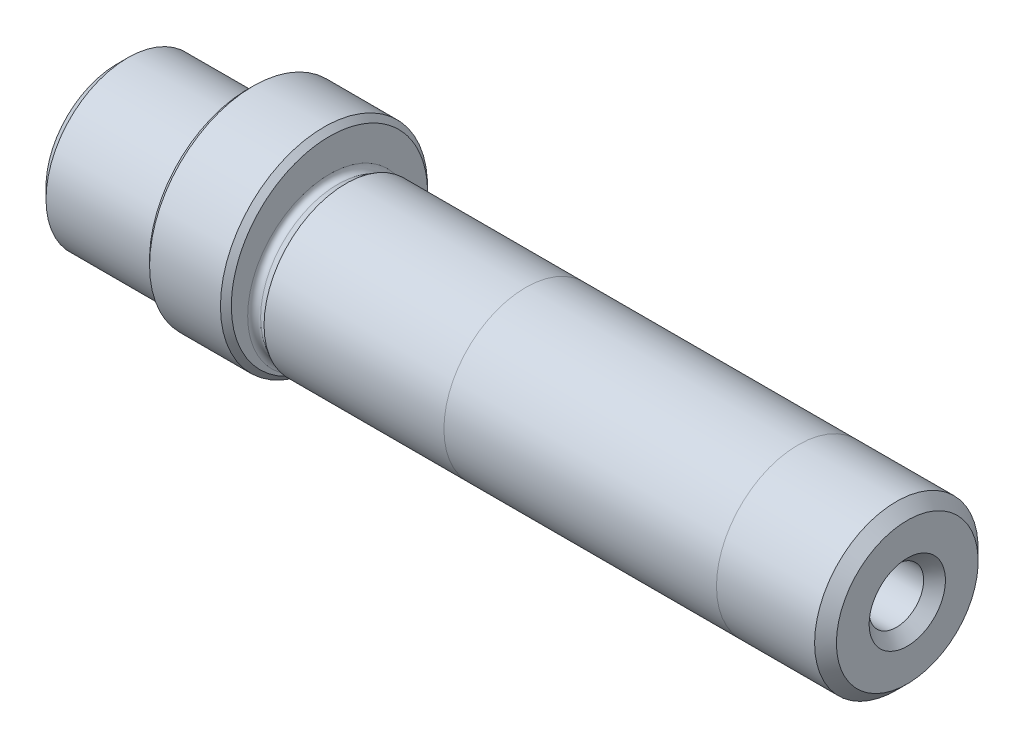
SolidWorks part; units mm, degrees
material "Cast Carbon Steel"
ref_plane "Front Plane" through (0, 0, 0) normal (0, 0, 1) x (1, 0, 0)
ref_plane "Top Plane" through (0, 0, 0) normal (0, 1, 0) x (1, 0, 0)
ref_plane "Right Plane" through (0, 0, 0) normal (1, 0, 0) x (0, 0, -1)
sketch "Sketch2" plane through (0, 0, 0) normal (0, 0, 1) x (1, 0, 0)
  line L0 (0, 0) -> (145, 0)
  line L1 (145, 0) -> (145, 15)
  line L2 (145, 15) -> (39, 15)
  line L3 (39, 15) -> (39, 25)
  line L4 (39, 25) -> (24, 25)
  line L5 (24, 25) -> (24, 15.2)
  line L6 (24, 15.2) -> (0, 15.2)
  line L7 (0, 15.2) -> (0, 0)
  line L8 (20, -25.2984) -> (20, 61.1316) construction
  dimension "D1" = 145
  dimension "D2" = 15
  dimension "D3" = 15
  dimension "D4" = 20
  dimension "D5" = 15.2
  dimension "D6" = 25
  dimension "D7" = 4
revolve "Revolve1" add sketch "Sketch2" angle 360 about L0
sketch "Sketch3" plane through (24, 0, 0) normal (-1, 0, 0) x (0, 0, 1)
  line L0 (0, 0) -> (0, 23.8099) construction
  circle A0 centre (0, 3) radius 19
  dimension "D1" = 38
  dimension "D2" = 3
extrude "Cut-Extrude1" cut sketch "Sketch3" against normal through all both and the other way through all flip side to cut
sketch "Sketch4" plane through (0, 0, 0) normal (0, 0, 1) x (1, 0, 0)
  line L0 (-1.2271, 15) -> (21, 15)
  line L1 (21, 15) -> (22.5, 14.134)
  line L2 (24, 15) -> (24, 19.0868)
  line L3 (24, 19.0868) -> (-1.2271, 19.0868)
  line L4 (-1.2271, 19.0868) -> (-1.2271, 15)
  line L5 (24, 22) -> (24, -16) construction
  line L6 (0, 0) -> (19.6384, 0) construction
  line L7 (147.3282, 15) -> (42, 15)
  line L8 (42, 15) -> (40.5, 14.134)
  line L9 (39, 15) -> (39, 21.5061)
  line L10 (39, 21.5061) -> (147.3282, 21.5061)
  line L11 (147.3282, 21.5061) -> (147.3282, 15)
  line L12 (39, -16) -> (39, 22) construction
  arc A0 (22.5, 14.134) -> (24, 15) centre (23, 15) ccw
  arc A1 (40.5, 14.134) -> (39, 15) centre (40, 15) cw
  dimension "D4" = 1
  dimension "D8" = 1
  dimension "D1" = 15
  dimension "D2" = 30
  dimension "D3" = 3
  dimension "D5" = 30
  dimension "D6" = 3
  dimension "D7" = 15
revolve "Cut-Revolve1" cut sketch "Sketch4" angle 360 about L6
chamfer "Chamfer1" distance 1 angle 45 2 edges at (39, 3, 19) (24, 3, -19)
sketch "Sketch6" plane through (0, 0, 0) normal (-1, 0, 0) x (0, 0, 1)
  circle A0 centre (0, 0) radius 5
  dimension "D1" = 10
extrude "Cut-Extrude2" cut sketch "Sketch6" against normal through all both
chamfer "Chamfer3" distance 2 angle 45 4 edges at (145, 0, 15) (145, 0, 5) (0, 0, -15) (0, 0, 5)
sketch "Sketch7" plane through (0, 0, 0) normal (0, 0, 1) x (1, 0, 0)
  line L0 (69, -23.1105) -> (69, 33.4965) construction
  line L1 (145, -13) -> (145, 13) construction
  line L2 (75, 36.786) -> (75, -23.1105)
  line L3 (125, 24.7245) -> (125, -23.1105)
  dimension "D1" = 76
  dimension "D2" = 70
  dimension "D3" = 50
split line "Split Line1"
